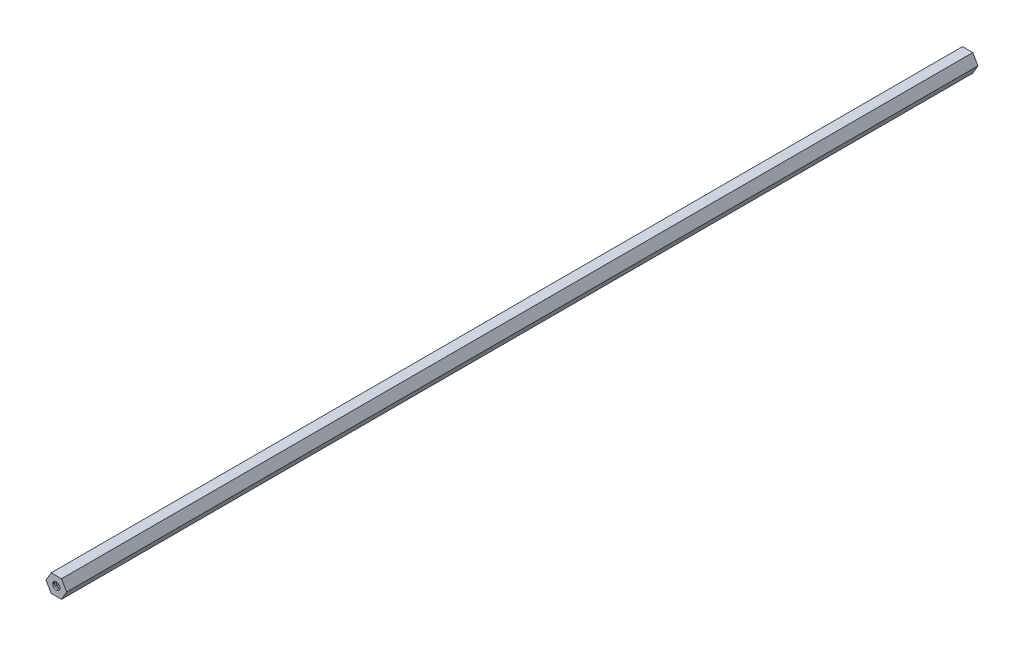
SolidWorks part; units mm, degrees
material "7075-T6 (SN)"
ref_plane "Alzado" through (0, 0, 0) normal (0, 0, 1) x (1, 0, 0)
ref_plane "Planta" through (0, 0, 0) normal (0, 1, 0) x (1, 0, 0)
ref_plane "Vista lateral" through (0, 0, 0) normal (1, 0, 0) x (0, 0, -1)
sketch "Croquis2" plane through (0, 0, 0) normal (0, 0, 1) x (1, 0, 0)
  line L1 (3.6662, -6.35) -> (7.3323, 0)
  line L2 (7.3323, 0) -> (3.6662, 6.35)
  line L3 (3.6662, 6.35) -> (-3.6662, 6.35)
  line L4 (-3.6662, 6.35) -> (-7.3323, 0)
  line L5 (-7.3323, 0) -> (-3.6662, -6.35)
  line L6 (-3.6662, -6.35) -> (3.6662, -6.35)
  circle A0 centre (0, 0) radius 6.35 construction
  dimension "D1" = 12.7
extrude "Extrusión Hex Profile" add sketch "Croquis2" along normal mid plane 647.7
sketch "Croquis3" plane through (0, 0, 0) normal (0, 0, 1) x (1, 0, 0)
  circle A0 centre (0, 0) radius 2.5527
  dimension "D1" = 5.1054
extrude "Tap Hole 1" cut sketch "Croquis3" against normal blind 19.05 from surface starting at face at (0, 0, 323.85)
extrude "Tap Hole 2" cut sketch "Croquis3<3>" along normal blind 19.05 from surface starting at face at (0, 0, -323.85)
sketch "Croquis3<3>" plane through (0, 0, 0) normal (0, 0, 1) x (1, 0, 0) same geometry as "Croquis3"
sketch "Croquis7" plane through (0, 0, 0) normal (0, 0, 1) x (1, 0, 0)
  circle A0 centre (0, 0) radius 6.8707
  dimension "D1" = 13.7414
extrude "ThunderHex" [suppressed] cut sketch "Croquis7" against normal through all both and the other way through all flip side to cut
sketch "Croquis8" plane through (0, 0, 0) normal (0, 1, 0) x (1, 0, 0)
  line L0 (0, -323.85) -> (-5.5562, -323.85) construction
  line L1 (3.6662, -323.85) -> (-3.6662, -323.85) construction
  line L3 (0, -323.85) -> (0, 0) construction
  line L4 (-5.5562, -323.85) -> (-6.35, -323.0562)
  line L5 (-6.35, -323.0562) -> (-6.35, -322.2625)
  line L6 (-6.35, -322.2625) -> (-5.9055, -322.2625)
  line L7 (-5.9055, -322.2625) -> (-5.9055, -320.675)
  line L8 (-5.9055, -320.675) -> (-12.7, -320.675)
  line L9 (-12.7, -320.675) -> (-12.7, -323.85)
  line L10 (-12.7, -323.85) -> (-5.5562, -323.85)
  line L11 (-3.6662, -323.85) -> (-7.3323, -323.85) construction
  dimension "D1" = 11.811
  dimension "D2" = 12.7
  dimension "D3" = 45
  dimension "D4" = 0.7937
  dimension "D6" = 0.7937
  dimension "D7" = 3.175
  dimension "D8" = 25.4
revolve "Retaining Ring 1" [suppressed] cut sketch "Croquis8" angle 360 about L3
sketch "Croquis9" plane through (0, 0, 0) normal (0, -1, 0) x (1, 0, 0)
  line L0 (0, -323.85) -> (-5.5562, -323.85) construction
  line L3 (0, -323.85) -> (0, 0) construction
  line L4 (-5.5562, -323.85) -> (-6.35, -323.0562)
  line L5 (-6.35, -323.0562) -> (-6.35, -322.2625)
  line L6 (-6.35, -322.2625) -> (-5.9055, -322.2625)
  line L7 (-5.9055, -322.2625) -> (-5.9055, -320.675)
  line L8 (-5.9055, -320.675) -> (-12.7, -320.675)
  line L9 (-12.7, -320.675) -> (-12.7, -323.85)
  line L10 (-12.7, -323.85) -> (-5.5562, -323.85)
  line L12 (-3.6662, -323.85) -> (3.6662, -323.85) construction
  line L13 (-7.3323, -323.85) -> (-3.6662, -323.85) construction
  dimension "D1" = 11.811
  dimension "D2" = 12.7
  dimension "D3" = 45
  dimension "D4" = 0.7937
  dimension "D6" = 0.7937
  dimension "D7" = 3.175
  dimension "D8" = 25.4
revolve "Retaining Ring 2" [suppressed] cut sketch "Croquis9" angle 360 about L3
sketch "Croquis10" plane through (0, 0, 0) normal (0, 1, 0) x (1, 0, 0)
  line L0 (0, -323.85) -> (0, 0) construction
  line L1 (3.6662, -323.85) -> (-3.6662, -323.85) construction
  line L2 (0, -323.85) -> (-5.5562, -323.85) construction
  line L3 (-3.6662, -323.85) -> (-7.3323, -323.85) construction
  line L4 (-5.5562, -323.85) -> (-6.35, -323.0562)
  line L5 (-6.35, -323.0562) -> (-6.35, -315.8998)
  line L6 (-6.35, -315.8998) -> (-9.525, -315.8998)
  line L7 (-9.525, -315.8998) -> (-9.525, -323.85)
  line L8 (-9.525, -323.85) -> (-5.5562, -323.85)
  dimension "D2" = 12.7
  dimension "D1" = 45
  dimension "D3" = 0.7937
  dimension "D4" = 7.9502
  dimension "D5" = 19.05
revolve "Round End 1" [suppressed] cut sketch "Croquis10" angle 360 about L0
sketch "Croquis12" plane through (0, 0, 0) normal (0, -1, 0) x (1, 0, 0)
  line L0 (0, -323.85) -> (0, 0) construction
  line L2 (0, -323.85) -> (-5.5562, -323.85) construction
  line L4 (-5.5562, -323.85) -> (-6.35, -323.0562)
  line L5 (-6.35, -323.0562) -> (-6.35, -315.8998)
  line L6 (-6.35, -315.8998) -> (-9.525, -315.8998)
  line L7 (-9.525, -315.8998) -> (-9.525, -323.85)
  line L8 (-9.525, -323.85) -> (-5.5562, -323.85)
  line L9 (-3.6662, -323.85) -> (3.6662, -323.85) construction
  dimension "D1" = 45
  dimension "D3" = 0.7937
  dimension "D4" = 7.9502
  dimension "D2" = 12.7
  dimension "D5" = 19.05
revolve "Round End 2" [suppressed] cut sketch "Croquis12" angle 360 about L0
thread "Rosca1" pitch 1.27 method cut profile "Perfil de rosca1" start angle 0, offset 0, length 0, pitch 1.27, diameter 5.1054
ref_plane "Plano1" through (2.5527, 0, -323.85) normal (0, -1, 0) x (1, 0, 0)
sketch "Perfil de rosca1" plane through (2.5527, 0, -323.85) normal (0, -1, 0) x (1, 0, 0)
  line L0 (0, 0) -> (0, 1.27) construction
  line L1 (0, 0) -> (0.6874, 0.3969)
  line L2 (0.6874, 0.3969) -> (0.6874, 0.5556)
  line L3 (0.6874, 0.5556) -> (0, 0.9525)
  line L4 (0.6874, 0.4762) -> (0, 0.4762) construction
  line L11 (0, 0) -> (0, 0.9525)
  point P2 (0, 0)
  dimension "Pitch" = 1.27
  dimension "Profile_Angle" = 60
  dimension "Profile_Land" = 0.1588
  dimension "Profile_Height" = 0.6874
thread "Rosca2" pitch 1.27 method cut profile "Perfil de rosca2" start angle 0, offset 0, length 0, pitch 1.27, diameter 5.1054
ref_plane "Plano2" through (-2.5527, 0, 323.85) normal (0, -1, 0) x (-1, 0, 0)
sketch "Perfil de rosca2" plane through (-2.5527, 0, 323.85) normal (0, -1, 0) x (-1, 0, 0)
  line L0 (0, 0) -> (0, 1.27) construction
  line L1 (0, 0) -> (0.6874, 0.3969)
  line L2 (0.6874, 0.3969) -> (0.6874, 0.5556)
  line L3 (0.6874, 0.5556) -> (0, 0.9525)
  line L4 (0.6874, 0.4762) -> (0, 0.4762) construction
  line L11 (0, 0) -> (0, 0.9525)
  point P2 (0, 0)
  dimension "Pitch" = 1.27
  dimension "Profile_Angle" = 60
  dimension "Profile_Land" = 0.1588
  dimension "Profile_Height" = 0.6874
equation "\"HexOD\"= 0.5pulgadas"
equation "\"Largo\"= 25.5pulgadas"
equation "\"D1@Croquis2\"=\"HexOD\""
equation "\"D1@Extrusión Hex Profile\" = \"Largo\""
equation "\"TapHole\"= IIF ( \"HexOD\" = 0.5pulgadas , 0.2010pulgadas , 0.190pulgadas )"
equation "\"D1@Croquis3\"=\"TapHole\""
equation "\"ProTapHole\"= 0.75pulgadas"
equation "\"D1@Tap Hole 1\" = \"ProTapHole\""
equation "\"D1@Tap Hole 2\" = \"ProTapHole\""
equation "\"ThunderHex\"= IIF ( \"HexOD\" = 0.5pulgadas , 0.541pulgadas , 0.4035pulgadas )"
equation "\"D1@Croquis7\"=\"ThunderHex\""
equation "\"D2@Croquis8\"=\"HexOD\""
equation "\"D1@Croquis8\"=if(\"HexOD\"=0.5pulgadas, 0.465pulgadas, 0.35pulgadas )"
equation "\"D2@Croquis9\"=\"HexOD\""
equation "\"D1@Croquis9\"=if(\"HexOD\"=0.5pulgadas, 0.465pulgadas, 0.35pulgadas )"
equation "\"D8@Croquis8\"=\"HexOD\"*2"
equation "\"D8@Croquis9\"=\"HexOD\"*2"
equation "\"D5@Croquis10\"=\"HexOD\"*1.5"
equation "\"D5@Croquis12\"=\"HexOD\"*1.5"
equation "\"D4@Croquis10\"=if( \"D2@Croquis10\"=<0.375, 0.28, 0.313)"
equation "\"D4@Croquis12\"=if( \"D2@Croquis10\"=<0.375, 0.28, 0.313)"
